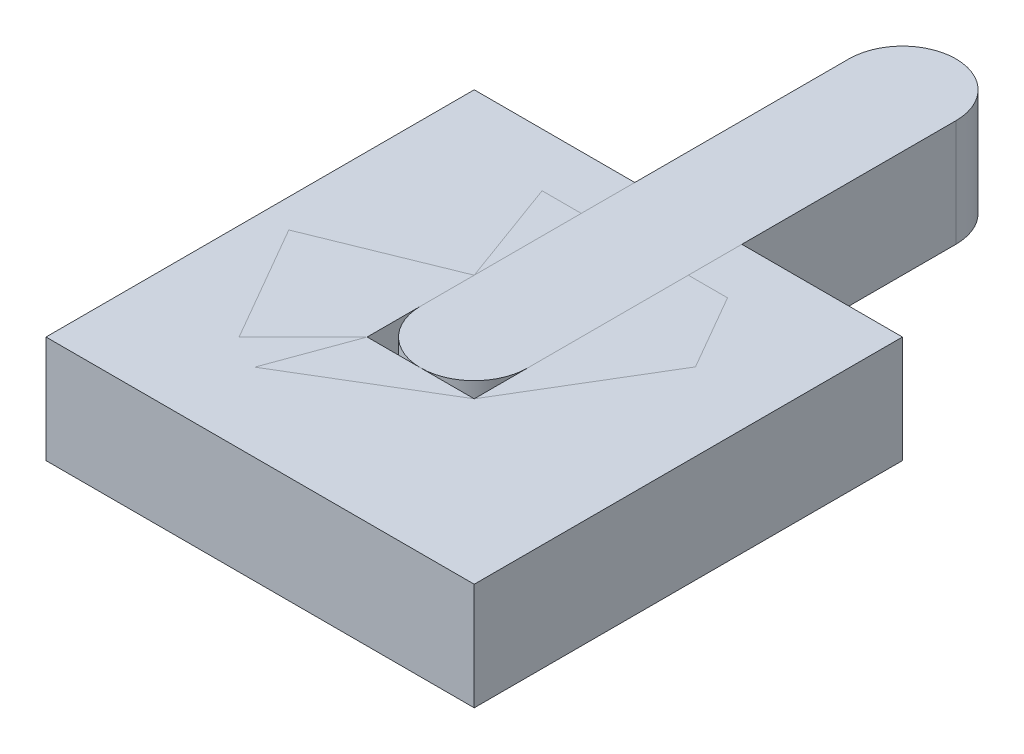
SolidWorks part; units mm, degrees
ref_plane "Front Plane" through (0, 0, 0) normal (0, 0, 1) x (1, 0, 0)
ref_plane "Top Plane" through (0, 0, 0) normal (0, 1, 0) x (1, 0, 0)
ref_plane "Right Plane" through (0, 0, 0) normal (1, 0, 0) x (0, 0, -1)
sketch "Sketch1" plane through (0, 0, 0) normal (0, 1, 0) x (1, 0, 0)
  line L0 (0, 0) -> (0, 9.2) construction
  line L1 (-1.15, 0) -> (-1.15, 9.2)
  line L2 (1.15, 0) -> (1.15, 9.2)
  arc A0 (-1.15, 0) -> (1.15, 0) centre (0, 0) ccw
  arc A1 (1.15, 9.2) -> (-1.15, 9.2) centre (0, 9.2) ccw
  point P3 (0, 4.6)
  dimension "D2" = 1.15
  dimension "D1" = 9.2
base flange "Base-Flange1" sketch "Sketch1" thickness 2.3 reverse thickness direction no parameters "D1"=0.7366
sketch "Sketch6" plane through (0, 0, 0) normal (0, 1, 0) x (1, 0, 0)
  line L1 (-4.6, -4.6) -> (4.6, -4.6)
  line L2 (-4.6, -4.6) -> (-4.6, 4.6)
  line L3 (-4.6, 4.6) -> (4.6, 4.6)
  line L4 (4.6, -4.6) -> (4.6, 4.6)
  line L5 (-4.6, -4.6) -> (4.6, 4.6) construction
  line L6 (-4.6, 4.6) -> (4.6, -4.6) construction
  point P0 (0, 0)
  dimension "D1" = 9.2
  dimension "D2" = 9.2
base flange "Base-Flange2" sketch "Sketch6" thickness 2.3 reverse thickness direction no parameters "D1"=0.7366
sketch "Sketch9" plane through (0, 0, 0) normal (0, 1, 0) x (1, 0, 0)
  line L1 (-1.15, -1.15) -> (1.15, -1.15)
  line L2 (-1.15, -1.15) -> (-1.15, 1.15)
  line L3 (-1.15, 1.15) -> (1.15, 1.15)
  line L4 (1.15, -1.15) -> (1.15, 1.15)
  line L5 (-1.15, -1.15) -> (1.15, 1.15) construction
  line L6 (-1.15, 1.15) -> (1.15, -1.15) construction
  point P0 (0, 0)
  dimension "D1" = 2.3
  dimension "D2" = 2.3
extrude "Cut-Extrude1" cut sketch "Sketch9" against normal up to next (2.3 mm away)
sketch "Sketch10" plane through (0, 0, 0) normal (0, 1, 0) x (1, 0, 0)
  line L1 (3.9837, 0) -> (1.9919, 3.45)
  line L2 (1.9919, 3.45) -> (-1.9919, 3.45)
  line L3 (-1.9919, 3.45) -> (-3.9837, 0)
  line L4 (-3.9837, 0) -> (-1.9919, -3.45)
  line L5 (-1.9919, -3.45) -> (1.9919, -3.45)
  line L6 (1.9919, -3.45) -> (3.9837, 0)
  circle A0 centre (0, 0) radius 3.45 construction
  dimension "D1" = 6.9
base flange "Base-Flange3" sketch "Sketch10" thickness 2.3 reverse thickness direction no parameters "D1"=0.7366
sketch "Sketch13" plane through (0, 0, 0) normal (0, 1, 0) x (1, 0, 0)
  line L1 (-1.15, -1.15) -> (1.15, -1.15)
  line L2 (-1.15, -1.15) -> (-1.15, 1.15)
  line L3 (-1.15, 1.15) -> (1.15, 1.15)
  line L4 (1.15, -1.15) -> (1.15, 1.15)
  line L5 (-1.15, -1.15) -> (1.15, 1.15) construction
  line L6 (-1.15, 1.15) -> (1.15, -1.15) construction
  point P0 (0, 0)
  dimension "D1" = 2.3
  dimension "D2" = 2.3
extrude "Cut-Extrude2" cut sketch "Sketch13" against normal through all
sketch "Bend-Lines1" [suppressed] plane through (0, 0, 0) normal (0, 1, 0) x (1, 0, 0)
sketch "Bounding-Box1" [suppressed] plane through (0, 0, 0) normal (0, 1, 0) x (1, 0, 0)
sheet metal parameters "Sheet-Metal1" thickness 2.3 parameters "D1"=0.7366
flat pattern "Flat-Pattern1" [suppressed]
sketch "Bend-Lines2" plane through (0, 0, 0) normal (0, 1, 0) x (1, 0, 0)
sketch3d "Bounding-Box2" [suppressed]
  line L0 (-1.15, 10.35, 0) -> (-1.15, -1.15, 0) construction
  line L1 (1.15, 10.35, 0) -> (1.15, -1.15, 0) construction
  line L2 (-1.15, 10.35, 0) -> (1.15, 10.35, 0) construction
  line L3 (-1.15, -1.15, 0) -> (1.15, -1.15, 0) construction
sheet metal parameters "Sheet-Metal2" thickness 2.3 parameters "D1"=0.7366
flat pattern "Flat-Pattern2"
sketch "Bend-Lines3" plane through (0, 0, 0) normal (0, 1, 0) x (1, 0, 0)
sketch3d "Bounding-Box3" [suppressed]
  line L0 (4.6, -4.6, 0) -> (4.6, 4.6, 0) construction
  line L1 (-4.6, -4.6, 0) -> (-4.6, 4.6, 0) construction
  line L2 (4.6, -4.6, 0) -> (-4.6, -4.6, 0) construction
  line L3 (4.6, 4.6, 0) -> (-4.6, 4.6, 0) construction
sheet metal parameters "Sheet-Metal3" thickness 2.3 parameters "D1"=0.7366
flat pattern "Flat-Pattern2"
sketch "Bend-Lines3" plane through (0, 0, 0) normal (0, 1, 0) x (1, 0, 0)
sketch3d "Bounding-Box3" [suppressed]
  line L0 (-4.6, -4.6, 0) -> (-4.6, 4.6, 0) construction
  line L1 (4.6, -4.6, 0) -> (4.6, 4.6, 0) construction
  line L2 (-4.6, -4.6, 0) -> (4.6, -4.6, 0) construction
  line L3 (-4.6, 4.6, 0) -> (4.6, 4.6, 0) construction
sheet metal parameters "Sheet-Metal4" thickness 2.3 parameters "D1"=0.7366
flat pattern "Flat-Pattern4"
sketch "Bend-Lines4" plane through (0, 0, 0) normal (0, 1, 0) x (1, 0, 0)
sketch3d "Bounding-Box4" [suppressed]
  line L0 (3.9837, -3.45, 0) -> (-3.9837, -3.45, 0) construction
  line L1 (3.9837, 3.45, 0) -> (-3.9837, 3.45, 0) construction
  line L2 (3.9837, -3.45, 0) -> (3.9837, 3.45, 0) construction
  line L3 (-3.9837, -3.45, 0) -> (-3.9837, 3.45, 0) construction
sheet metal parameters "Sheet-Metal5" thickness 2.3 parameters "D1"=0.7366
flat pattern "Flat-Pattern4"
sketch "Bend-Lines4" plane through (0, 0, 0) normal (0, 1, 0) x (1, 0, 0)
sketch3d "Bounding-Box4" [suppressed]
  line L0 (3.9837, -3.45, 0) -> (-3.9837, -3.45, 0) construction
  line L1 (3.9837, 3.45, 0) -> (-3.9837, 3.45, 0) construction
  line L2 (3.9837, -3.45, 0) -> (3.9837, 3.45, 0) construction
  line L3 (-3.9837, -3.45, 0) -> (-3.9837, 3.45, 0) construction
